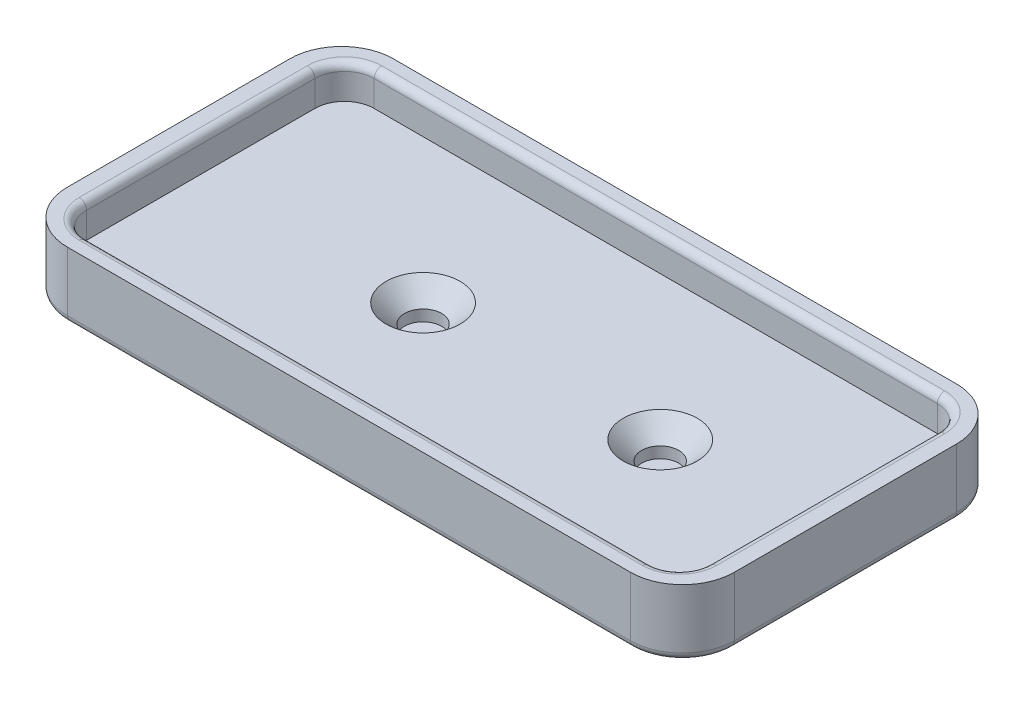
SolidWorks part; units mm, degrees
ref_plane "Спереди" through (0, 0, 0) normal (0, 0, 1) x (1, 0, 0)
ref_plane "Сверху" through (0, 0, 0) normal (0, 1, 0) x (1, 0, 0)
ref_plane "Справа" through (0, 0, 0) normal (1, 0, 0) x (0, 0, -1)
sketch "Эскиз1" plane through (0, 0, 0) normal (0, 1, 0) x (1, 0, 0)
  line L1 (-45, -22) -> (45, -22)
  line L2 (-45, -22) -> (-45, 22)
  line L3 (-45, 22) -> (45, 22)
  line L4 (45, -22) -> (45, 22)
  line L5 (0, 22) -> (0, -22) construction
  line L6 (-45, 0) -> (45, 0) construction
  point P0 (0, 0)
  dimension "D1" = 44
  dimension "D2" = 90
extrude "Бобышка-Вытянуть1" add sketch "Эскиз1" along normal blind 9
fillet "Скругление1" radius 7 4 edges at (-45, 4.5, -22) (-45, 4.5, 22) (45, 4.5, -22) (45, 4.5, 22)
sketch "Эскиз2" plane through (0, 9, 0) normal (0, 1, 0) x (1, 0, 0)
  line L1 (-42, -19.4) -> (42, -19.4)
  line L2 (-42, -19.4) -> (-42, 19.4)
  line L3 (-42, 19.4) -> (42, 19.4)
  line L4 (42, -19.4) -> (42, 19.4)
  line L5 (0, 19.4) -> (0, -19.4) construction
  line L6 (-42, 0) -> (42, 0) construction
  point P0 (0, 0)
  dimension "D1" = 84
  dimension "D2" = 38.8
extrude "Вырез-Вытянуть1" cut sketch "Эскиз2" against normal blind 4.5
sketch "Эскиз3" plane through (0, 4.5, 0) normal (0, 1, 0) x (1, 0, 0)
  line L0 (0, 15.7954) -> (0, 0) construction
  line L1 (0, 0) -> (50.7445, 0) construction
  circle A0 centre (20, 0) radius 2.5
  circle A1 centre (-12, 0) radius 2.5
  dimension "D1" = 5
  dimension "D2" = 32
  dimension "D3" = 20
extrude "Вырез-Вытянуть2" cut sketch "Эскиз3" against normal blind 4
chamfer "Фаска1" distance 2.5 angle 45 2 edges at (-12, 4.5, -2.5) (20, 4.5, 2.5)
fillet "Скругление2" radius 4 4 edges at (-42, 6.75, 19.4) (42, 6.75, 19.4) (42, 6.75, -19.4) (-42, 6.75, -19.4)
fillet "Скругление3" radius 1 8 edges at (40.8284, 9, -18.2284) (42, 9, 0) (40.8284, 9, 18.2284) (0, 9, 19.4) (-40.8284, 9, 18.2284) (-42, 9, 0) (-40.8284, 9, -18.2284) (0, 9, -19.4)
fillet "Скругление4" radius 1 8 edges at (-42.9497, 0, 19.9497) (0, 0, 22) (42.9497, 0, 19.9497) (45, 0, 0) (42.9497, 0, -19.9497) (0, 0, -22) (-42.9497, 0, -19.9497) (-45, 0, 0)
